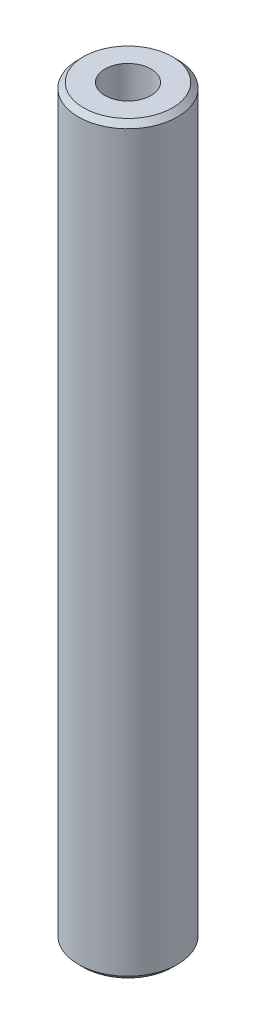
SolidWorks part; units mm, degrees
ref_plane "Front Plane" through (0, 0, 0) normal (0, 0, 1) x (1, 0, 0)
ref_plane "Top Plane" through (0, 0, 0) normal (0, 1, 0) x (1, 0, 0)
ref_plane "Right Plane" through (0, 0, 0) normal (1, 0, 0) x (0, 0, -1)
sketch "Sketch1" plane through (0, 0, 0) normal (0, 1, 0) x (1, 0, 0)
  circle A0 centre (0, 0) radius 40
  dimension "SHAFT_OD" = 80
extrude "Boss-Extrude1" add sketch "Sketch1" along normal blind 600
sketch "Sketch2" plane through (0, 0, 0) normal (0, 1, 0) x (1, 0, 0)
  circle A0 centre (0, 0) radius 18.5778
  dimension "BORE_D" = 37.1556
extrude "Cut-Extrude1" cut sketch "Sketch2" along normal through all
chamfer "Chamfer1" distance 4.2198 angle 45 2 edges at (0, 600, 40) (0, 0, 40)
